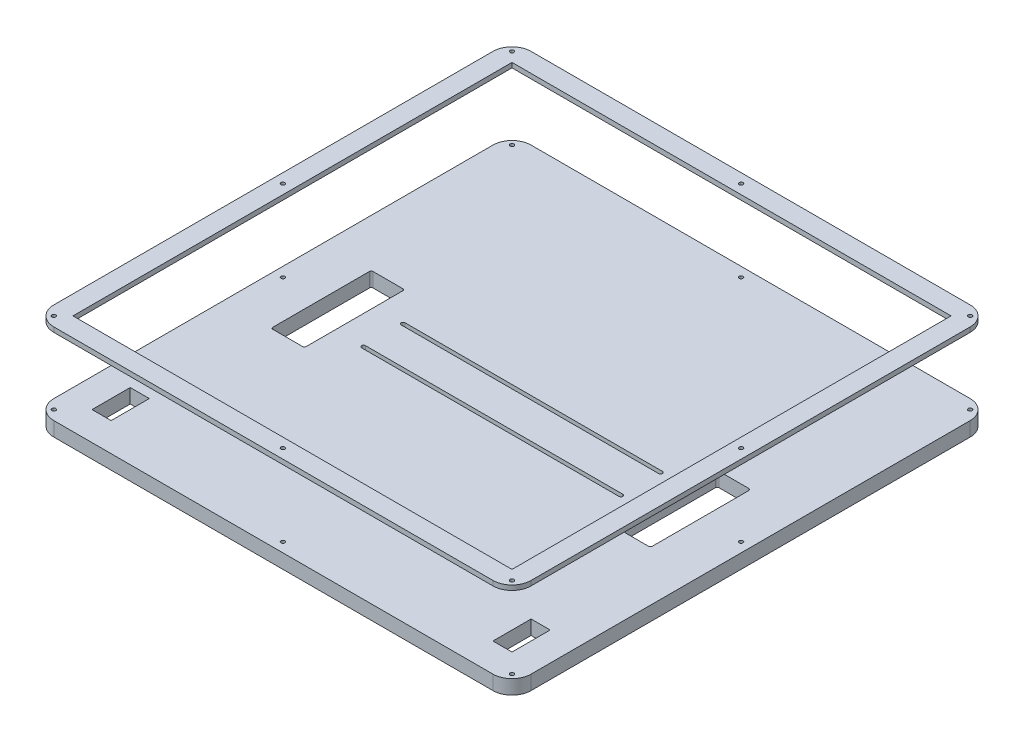
SolidWorks part; units mm, degrees
ref_plane "Front Plane" through (0, 0, 0) normal (0, 0, 1) x (1, 0, 0)
ref_plane "Top Plane" through (0, 0, 0) normal (0, 1, 0) x (1, 0, 0)
ref_plane "Right Plane" through (0, 0, 0) normal (1, 0, 0) x (0, 0, -1)
sketch "Sketch1" plane through (0, 0, 0) normal (0, 1, 0) x (1, 0, 0)
  line L1 (-230, -250) -> (230, -250)
  line L2 (-250, -230) -> (-250, 230)
  line L3 (-230, 250) -> (230, 250)
  line L4 (250, -230) -> (250, 230)
  line L5 (-250, -250) -> (250, 250) construction
  line L6 (-250, 250) -> (250, -250) construction
  line L7 (0, 250) -> (0, -250) construction
  line L8 (-250, 0) -> (250, 0) construction
  line L9 (-198, -52.5) -> (-167, -52.5)
  line L10 (-200, -50.5) -> (-200, 50.5)
  line L11 (-198, 52.5) -> (-167, 52.5)
  line L12 (-165, -50.5) -> (-165, 50.5)
  line L13 (-200, -52.5) -> (-165, 52.5) construction
  line L14 (-200, 52.5) -> (-165, -52.5) construction
  line L15 (195.5, -52.5) -> (164.5, -52.5)
  line L16 (197.5, -50.5) -> (197.5, 50.5)
  line L17 (195.5, 52.5) -> (164.5, 52.5)
  line L18 (162.5, -50.5) -> (162.5, 50.5)
  line L19 (197.5, -52.5) -> (162.5, 52.5) construction
  line L20 (197.5, 52.5) -> (162.5, -52.5) construction
  arc A0 (230, 250) -> (250, 230) centre (230, 230) cw
  arc A1 (250, -230) -> (230, -250) centre (230, -230) cw
  arc A2 (-230, -250) -> (-250, -230) centre (-230, -230) cw
  arc A3 (-250, 230) -> (-230, 250) centre (-230, 230) cw
  arc A10 (162.5, -50.5) -> (164.5, -52.5) centre (164.5, -50.5) ccw
  arc A11 (195.5, -52.5) -> (197.5, -50.5) centre (195.5, -50.5) ccw
  arc A12 (197.5, 50.5) -> (195.5, 52.5) centre (195.5, 50.5) ccw
  arc A13 (162.5, 50.5) -> (164.5, 52.5) centre (164.5, 50.5) cw
  arc A14 (-167, 52.5) -> (-165, 50.5) centre (-167, 50.5) cw
  arc A15 (-165, -50.5) -> (-167, -52.5) centre (-167, -50.5) cw
  arc A16 (-198, -52.5) -> (-200, -50.5) centre (-198, -50.5) cw
  arc A17 (-200, 50.5) -> (-198, 52.5) centre (-198, 50.5) cw
  circle A22 centre (-240, 240) radius 2
  circle A23 centre (240, 240) radius 2
  circle A24 centre (240, -240) radius 2
  circle A25 centre (-240, -240) radius 2
  circle A26 centre (-240, 0) radius 2
  circle A27 centre (240, 0) radius 2
  circle A28 centre (0, 240) radius 2
  circle A29 centre (0, -240) radius 2
  point P0 (0, 0)
  point P26 (180, 0)
  point P35 (-182.5, 0)
  point P77 (0, 0)
  dimension "D3" = 20
  dimension "D4" = 10
  dimension "D5" = 50
  dimension "D10" = 2
  dimension "D11" = 2
  dimension "D7" = 4
  dimension "D8" = 4
  dimension "D9" = 4
  dimension "D1" = 500
  dimension "D2" = 500
  dimension "D6" = 35
sketch "Sketch2" plane through (0, 0, 0) normal (0, 0, 1) x (1, 0, 0)
  line L0 (0, 0) -> (0, 80) construction
  dimension "D1" = 80
ref_plane "Plane1" through (0, 80, 0) normal (0, 1, 0) x (1, 0, 0)
sketch "Sketch3" plane through (0, 80, 0) normal (0, 1, 0) x (1, 0, 0)
  line L1 (-230, -250) -> (230, -250)
  line L2 (-250, -230) -> (-250, 230)
  line L3 (-230, 250) -> (230, 250)
  line L4 (250, -230) -> (250, 230)
  line L5 (-250, -250) -> (-230, -230) construction
  line L6 (-250, 250) -> (-230, 230) construction
  line L17 (0, -210) -> (0, -250) construction
  line L18 (230, -230) -> (-230, -230)
  line L19 (0, 250) -> (0, 210) construction
  line L24 (230, -230) -> (230, 230)
  line L25 (230, 230) -> (-230, 230)
  line L26 (230, 230) -> (250, 250) construction
  line L33 (230, -230) -> (250, -250) construction
  line L35 (-230, -230) -> (-230, 230)
  line L36 (230, -230) -> (-230, 230) construction
  line L37 (230, 230) -> (-230, -230) construction
  arc A0 (230, 250) -> (250, 230) centre (230, 230) cw
  arc A1 (250, -230) -> (230, -250) centre (230, -230) cw
  arc A2 (-230, -250) -> (-250, -230) centre (-230, -230) cw
  arc A3 (-250, 230) -> (-230, 250) centre (-230, 230) cw
  circle A4 centre (-240, 240) radius 2
  circle A5 centre (0, 240) radius 2
  circle A6 centre (240, 240) radius 2
  circle A7 centre (-240, 0) radius 2
  circle A8 centre (-240, -240) radius 2
  circle A9 centre (0, -240) radius 2
  circle A10 centre (240, -240) radius 2
  circle A11 centre (240, 0) radius 2
  point P0 (0, 0)
  point P19 (0, 0)
  point P20 (0, 0)
  point P21 (0, 0)
  point P32 (0, 0)
  point P39 (0, 0)
  dimension "D1" = 20
  dimension "D2" = 20
extrude "Boss-Extrude1" add sketch "Sketch1" against normal blind 15
extrude "Boss-Extrude2" add sketch "Sketch3" along normal blind 5 separate body contours A3 L2 A2 L1 A1 L4 A0 L3 region at (-243.6421, 80, 243.6421)
sketch "Sketch9" plane through (0, 0, 0) normal (0, 1, 0) x (1, 0, 0)
  line L0 (-250, -250) -> (250, 250) construction
  line L1 (-189.341, -89.341) -> (-89.341, -89.341)
  line L2 (-189.341, -89.341) -> (-189.341, -189.341)
  line L3 (-189.341, -189.341) -> (-89.341, -189.341)
  line L4 (-89.341, -89.341) -> (-89.341, -189.341)
  line L5 (-189.341, -89.341) -> (-89.341, -189.341) construction
  line L6 (-189.341, -189.341) -> (-89.341, -89.341) construction
  point P0 (-139.341, -139.341)
  dimension "D1" = 100
sketch "Sketch10" plane through (0, 0, 0) normal (0, 1, 0) x (1, 0, 0)
  line L4 (-55, 0) -> (55, 0) construction
  line L5 (0, -55) -> (0, 55) construction
  line L6 (0, 0) -> (67.0062, 0) construction
  line L7 (-134.8425, 22.75) -> (134.8425, 22.75)
  line L8 (134.8425, 18.75) -> (-134.8425, 18.75)
  line L9 (-134.8425, -18.75) -> (134.8425, -18.75)
  line L10 (134.8425, -22.75) -> (-134.8425, -22.75)
  arc A0 (-134.8425, 22.75) -> (-134.8425, 18.75) centre (-134.8425, 20.75) ccw
  arc A2 (-134.8425, -22.75) -> (-134.8425, -18.75) centre (-134.8425, -20.75) cw
  arc A3 (134.8425, -22.75) -> (134.8425, -18.75) centre (134.8425, -20.75) ccw
  arc A4 (134.8425, 22.75) -> (134.8425, 18.75) centre (134.8425, 20.75) cw
  dimension "D3" = 4
  dimension "D1" = 20.75
extrude "Cut-Extrude1" cut sketch "Sketch10" against normal up to next (15 mm away)
sketch "Sketch11" plane through (0, 0, 0) normal (0, 1, 0) x (1, 0, 0)
  line L0 (230, -230) -> (-230, -230) construction
  line L1 (-220, -220) -> (-200, -220)
  line L2 (-220, -220) -> (-220, -180)
  line L3 (-220, -180) -> (-200, -180)
  line L4 (-200, -220) -> (-200, -180)
  line L9 (-230, -230) -> (-230, 230) construction
  point P4 (-200, -200)
  point P5 (0, 0)
  dimension "D1" = 10
  dimension "D2" = 10
  dimension "D3" = 20
  dimension "D4" = 40
extrude "Cut-Extrude2" cut sketch "Sketch11" against normal up to next (15 mm away)
mirror "Mirror1" about plane through (0, 0, 0) normal (1, 0, 0) of "Cut-Extrude2"
